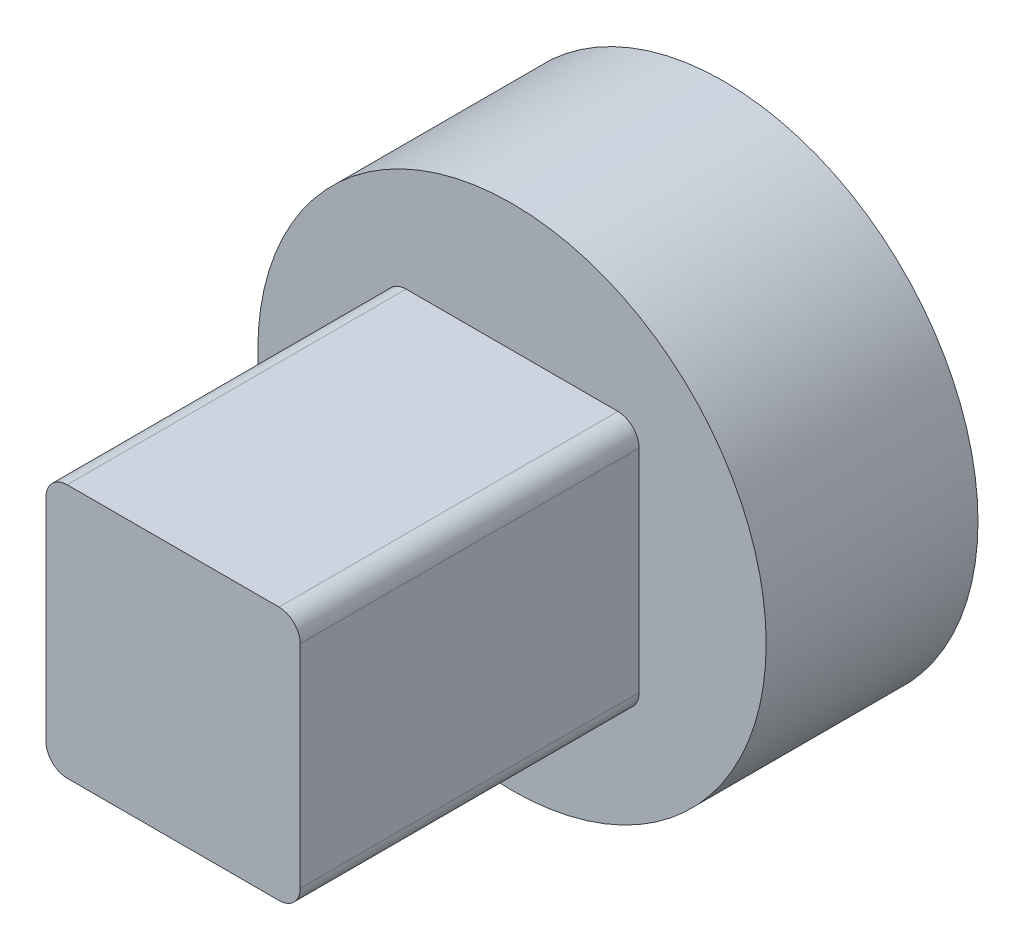
SolidWorks part; units mm, degrees
ref_plane "Front Plane" through (0, 0, 0) normal (0, 0, 1) x (1, 0, 0)
ref_plane "Top Plane" through (0, 0, 0) normal (0, 1, 0) x (1, 0, 0)
ref_plane "Right Plane" through (0, 0, 0) normal (1, 0, 0) x (0, 0, -1)
sketch "Sketch1" plane through (0, 0, -23.4655) normal (0, 0, 1) x (1, 0, 0)
  circle A0 centre (3.7405, -31.8284) radius 2.5
  circle A1 centre (3.7405, -31.8284) radius 6
extrude "Boss-Extrude1" add sketch "Sketch1" along normal blind 5
sketch "Sketch2" plane through (0, 0, -18.4655) normal (0, 0, 1) x (1, 0, 0)
  line L4 (3.7405, -31.8284) -> (6.7405, -31.8284) construction
  line L5 (6.7405, -31.8284) -> (6.7405, -28.8284) construction
  line L7 (6.2405, -28.8284) -> (1.2405, -28.8284)
  line L8 (6.7405, -29.3284) -> (6.7405, -34.3284)
  line L9 (6.2405, -34.8284) -> (1.2405, -34.8284)
  line L10 (0.7405, -29.3284) -> (0.7405, -34.3284)
  arc A1 (0.7405, -29.3284) -> (1.2405, -28.8284) centre (1.2405, -29.3284) cw
  arc A2 (1.2405, -34.8284) -> (0.7405, -34.3284) centre (1.2405, -34.3284) cw
  arc A3 (6.2405, -34.8284) -> (6.7405, -34.3284) centre (6.2405, -34.3284) ccw
  arc A4 (6.2405, -28.8284) -> (6.7405, -29.3284) centre (6.2405, -29.3284) cw
  point P6 (0.7405, -28.8284)
  point P12 (0.7405, -34.8284)
  point P15 (6.7405, -34.8284)
  dimension "D5" = 0.5
  dimension "D6" = 0.5
  dimension "D1" = 3
  dimension "D2" = 3
  dimension "D3" = 6
  dimension "D4" = 6
extrude "Boss-Extrude2" add sketch "Sketch2" along normal blind 8
